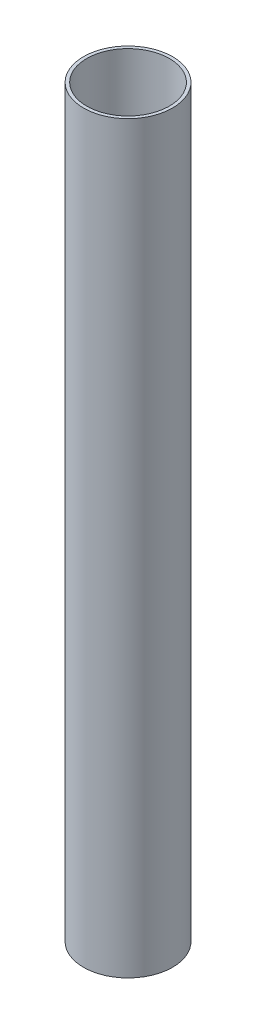
SolidWorks part; units mm, degrees
material "Thornel Mat VMA"
ref_plane "前视基准面" through (0, 0, 0) normal (0, 0, 1) x (1, 0, 0)
ref_plane "上视基准面" through (0, 0, 0) normal (0, 1, 0) x (1, 0, 0)
ref_plane "右视基准面" through (0, 0, 0) normal (1, 0, 0) x (0, 0, -1)
other "Configuration Table"
sketch "草图1" plane through (0, 0, 0) normal (0, 1, 0) x (1, 0, 0)
  circle A0 centre (0, 0) radius 20.1
  circle A1 centre (0, 0) radius 18.65
  dimension "D1" = 40.2
  dimension "D2" = 37.3
extrude "凸台-拉伸1" add sketch "草图1" along normal blind 336
ref_axis "基准轴1" through (0, 352.8, 0) along (0, -1, 0)
